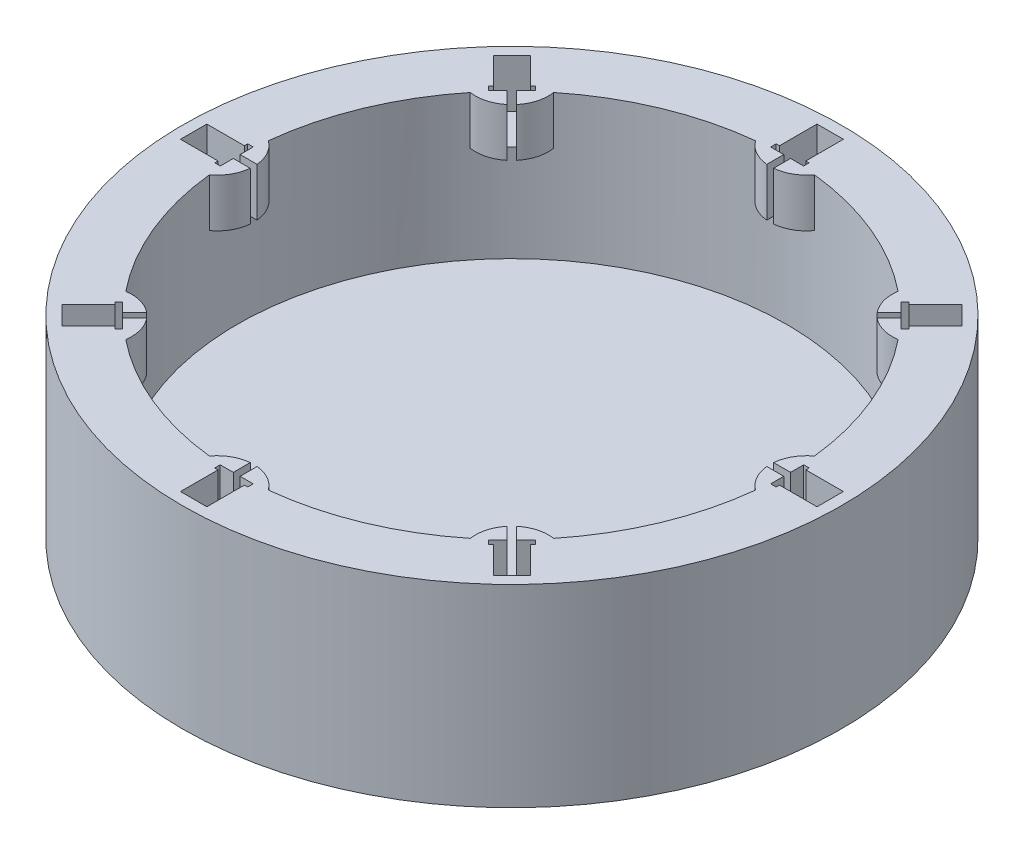
SolidWorks part; units mm, degrees
ref_plane "Front Plane" through (0, 0, 0) normal (0, 0, 1) x (1, 0, 0)
ref_plane "Top Plane" through (0, 0, 0) normal (0, 1, 0) x (1, 0, 0)
ref_plane "Right Plane" through (0, 0, 0) normal (1, 0, 0) x (0, 0, -1)
sketch "Sketch1" plane through (0, 0, 0) normal (0, 1, 0) x (1, 0, 0)
  circle A0 centre (0, 0) radius 38.1
  point P11 (0, 0)
  dimension "D1" = 76.2
extrude "Boss-Extrude1" add sketch "Sketch1" along normal blind 5.588
sketch "Sketch5" plane through (0, 5.588, 0) normal (0, 1, 0) x (1, 0, 0)
  circle A0 centre (0, 0) radius 38.1 construction
  circle A1 centre (0, 0) radius 38.1
  circle A2 centre (0, 0) radius 31.75
  dimension "D1" = 6.35
extrude "Boss-Extrude3" add sketch "Sketch5" along normal blind 16.764
sketch "Sketch3" plane through (0, 0, 0) normal (0, 0, 1) x (1, 0, 0)
  circle A0 centre (0, 19.05) radius 1.5494
  dimension "D2" = 3.0988
  dimension "D1" = 19.05
sketch "Sketch6" plane through (0, 22.352, 0) normal (0, 1, 0) x (1, 0, 0)
  line L0 (-1.524, -31.7134) -> (-1.524, -38.0695)
  line L1 (1.524, -31.7134) -> (1.524, -38.0695)
  line L2 (0, 0) -> (0, -9.6272) construction
  line L3 (-1.524, -36.7934) -> (1.524, -36.7934)
  line L4 (-0.3933, -31.818) -> (-0.3933, -29.8571)
  line L5 (1.9074, -32.453) -> (-1.9074, -32.453)
  line L6 (1.9074, -32.453) -> (1.9074, -31.818)
  line L7 (1.9074, -31.818) -> (-1.9074, -31.818)
  line L8 (-1.9074, -32.453) -> (-1.9074, -31.818)
  line L9 (0, -31.818) -> (0, -32.453) construction
  line L10 (1.9074, -32.1355) -> (-1.9074, -32.1355) construction
  line L11 (0.3933, -31.818) -> (0.3933, -29.8571)
  circle A0 centre (0, 0) radius 31.75 construction
  circle A1 centre (0, 0) radius 38.1 construction
  arc A2 (-1.524, -38.0695) -> (1.524, -38.0695) centre (0, 0) ccw
  arc A3 (-3.408, -31.5666) -> (3.408, -31.5666) centre (0, -34.0636) cw
  circle A4 centre (0, 0) radius 31.75
  point P11 (0, -32.1355)
  point P19 (0, -36.7934)
  circle M5 centre (0, 0) radius 31.75
  dimension "D1" = 3.048
  dimension "D2" = 5.08
  dimension "D3" = 0.635
extrude "Cut-Extrude2" cut sketch "Sketch6" against normal blind 5.588 contours L0 L3 L1 M5 | L1 L7 L0 L5 | L8 L5 L0 L7 | L6 L7 L1 L5 | L7 L11 L4 M5 region at (0, 22.352, 34.6232) region at (-1.7157, 22.352, 32.1355) region at (0, 22.352, 32.1355) region at (1.7157, 22.352, 32.1355) region at (0, 22.352, 31.7836)
extrude "Boss-Extrude4" add sketch "Sketch6<4>" against normal blind 5.588 contours A3 L4 M5 | A3 L11 M5 region at (-1.5396, 22.352, 30.9601) region at (1.5396, 22.352, 30.9601)
sketch "Sketch6<4>" plane through (0, 22.352, 0) normal (0, 1, 0) x (1, 0, 0) same geometry as "Sketch6"
pattern_circular "CirPattern1" count 8 over 360 about axis through (0, 22.352, 0) along (0, 1, 0) of "Cut-Extrude2", "Boss-Extrude4"
